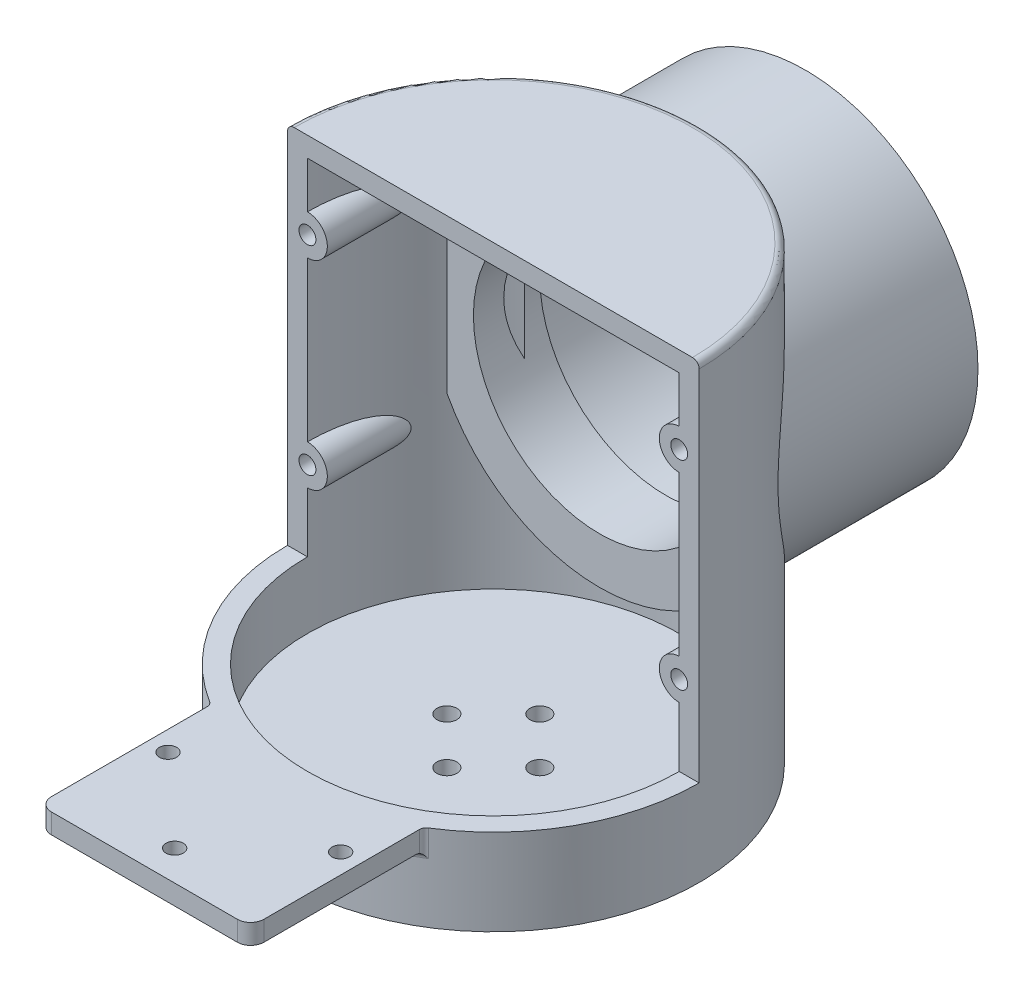
SolidWorks part; units mm, degrees
ref_plane "Спереди" through (0, 0, 0) normal (0, 0, 1) x (1, 0, 0)
ref_plane "Сверху" through (0, 0, 0) normal (0, 1, 0) x (1, 0, 0)
ref_plane "Справа" through (0, 0, 0) normal (1, 0, 0) x (0, 0, -1)
sketch "Эскиз3" plane through (0, 0, 0) normal (1, 0, 0) x (0, 0, -1)
  line L0 (0, 68.2882) -> (0, 0) construction
  line L1 (0, 0) -> (31, 0)
  line L2 (31, 0) -> (31, 68)
  line L3 (31, 68) -> (0, 68)
  line L4 (0, 68) -> (0, 65)
  line L5 (0, 65) -> (28, 65)
  line L6 (28, 65) -> (28, 3)
  line L7 (28, 3) -> (0, 3)
  line L8 (0, 3) -> (0, 0)
  dimension "D1" = 62
  dimension "D2" = 68
  dimension "D3" = 3
  dimension "D4" = 3
  dimension "D5" = 3
revolve "Повернуть2" add sketch "Эскиз3" angle 360 about L0
sketch "Эскиз4" plane through (0, 68, 0) normal (0, 1, 0) x (1, 0, 0)
  line L0 (-31, 0) -> (31, 0)
  circle A0 centre (0, 0) radius 31 construction
  arc A1 (31, 0) -> (-31, 0) centre (0, 0) cw
extrude "Вырез-Вытянуть1" cut sketch "Эскиз4" against normal blind 55
sketch "Эскиз6" plane through (0, 0, 0) normal (0, -1, 0) x (1, 0, 0)
  circle A0 centre (7, 0) radius 1.5
  dimension "D1" = 3
  dimension "D2" = 7
extrude "Вырез-Вытянуть3" cut sketch "Эскиз6" against normal up to surface (3 mm away) up to face at (0, 3, 28)
pattern_circular "Круговой массив1" count 4 over 360 about axis through (0, 68.2882, 0) along (0, 1, 0) of "Вырез-Вытянуть3"
sketch "Эскиз7" plane through (0, 0, 0) normal (0, 0, 1) x (1, 0, 0)
  circle A0 centre (0, 41) radius 21
  circle A1 centre (0, 41) radius 26
  dimension "D1" = 52
  dimension "D2" = 42
  dimension "D3" = 41
extrude "Бобышка-Вытянуть1" add sketch "Эскиз7" against normal blind 31 from offset 16 offset against normal yes
sketch "Эскиз8" plane through (0, 0, -47) normal (0, 0, -1) x (-1, 0, 0)
  circle A0 centre (0, 41) radius 21
  dimension "D1" = 42
  dimension "D2" = 41
extrude "Вырез-Вытянуть4" cut sketch "Эскиз8" against normal blind 25
sketch "Эскиз9" plane through (0, 13, 0) normal (0, 1, 0) x (1, 0, 0)
  line L0 (-16, -26.5518) -> (-16, -52.5518)
  line L1 (-16, -52.5518) -> (16, -52.5518)
  line L2 (16, -52.5518) -> (16, -26.5518)
  line L3 (0, 0) -> (0, -52.5518) construction
  arc A0 (16, -26.5518) -> (-16, -26.5518) centre (0, 0) cw
  arc A1 (-31, 0) -> (31, 0) centre (0, 0) ccw construction
  dimension "D1" = 26
  dimension "D2" = 32
extrude "Бобышка-Вытянуть2" add sketch "Эскиз9" against normal blind 3
fillet "Скругление1" radius 2 2 edges at (16, 11.5, 52.5518) (-16, 11.5, 52.5518)
fillet "Скругление2" radius 1 4 edges at (16, 11.5, 26.5518) (0, 10, 31) (-16, 11.5, 26.5518) (0, 68, -31)
sketch "Эскиз11" plane through (0, 0, 0) normal (0, 0, 1) x (1, 0, 0)
  line L0 (-28, 65) -> (-28, 13) construction
  line L1 (28, 13) -> (28, 65) construction
  line L3 (-28, 25) -> (28, 25) construction
  line L4 (-28, 25) -> (-28, 55) construction
  line L5 (-28, 55) -> (28, 55) construction
  line L6 (28, 25) -> (28, 55) construction
  circle A0 centre (-28, 55) radius 3
  circle A1 centre (-28, 25) radius 3
  circle A2 centre (28, 25) radius 3
  circle A3 centre (28, 55) radius 3
  point P12 (0, 25)
  point P15 (28, 40)
  dimension "D1" = 6
  dimension "D2" = 6
  dimension "D3" = 6
  dimension "D4" = 6
  dimension "D5" = 30
  dimension "D6" = 40
extrude "Бобышка-Вытянуть3" add sketch "Эскиз11" against normal up to surface (12.6095 mm away) up to face at (0.3812, 44.067, -10.9146)
hole_wizard "Сверло под метчик  спиральное M2.52" positions "Эскиз15" profile "Эскиз16" hole size "M2.5x0.45" standard "Ansi Metric"
sketch "Эскиз15" plane through (0, 0, 0) normal (0, 0, 1) x (1, 0, 0)
  point P0 (-28, 55)
  point P3 (28, 55)
  point P6 (28, 25)
  point P9 (-28, 25)
sketch "Эскиз16" plane through (-28, 55, 0) normal (1, 0, 0) x (0, -1, 0)
  line L0 (0, 0) -> (0, 5.7661)
  line L1 (0, 5.7661) -> (1.275, 5)
  line L2 (1.275, 5) -> (1.275, 0)
  line L5 (1.275, 0) -> (0, 0)
  line L10 (0, 5.7661) -> (-1.275, 5) construction
  line L11 (0, -6.35) -> (0, 107.95) construction
  dimension "Диаметр отверстия" = 2.55
  dimension "Глубина отверстия" = 5
  dimension "Угол заточки сверла" = 118
sketch "Эскиз17" plane through (0, 13, 0) normal (0, 1, 0) x (1, 0, 0)
  circle A0 centre (-13, -36) radius 1.3
  circle A1 centre (0, -48) radius 1.3
  circle A2 centre (13, -36) radius 1.3
  dimension "D1" = 2.6
  dimension "D2" = 36
  dimension "D3" = 12
  dimension "D4" = 13
  dimension "D5" = 26
extrude "Вырез-Вытянуть5" cut sketch "Эскиз17" against normal up to surface (3 mm away) up to face at (0, 10, 44.4581)
hole_wizard "Отверстие обработанное метчиком M2x0.41" positions "Эскиз18" profile "Эскиз19" tap size "M2x0.4" standard "HASCO Metric"
sketch "Эскиз18" plane through (0, 0, -47) normal (0, 0, -1) x (-1, 0, 0)
  line L2 (0, 41) -> (23, 41) construction
  line L4 (0, 41) -> (16.2635, 57.2635) construction
  circle A1 centre (0, 41) radius 23 construction
  point P0 (16.2635, 57.2635)
  dimension "D1" = 46
  dimension "D2" = 45
sketch "Эскиз19" plane through (-16.2635, 57.2635, -47) normal (1, 0, 0) x (0, 1, 0)
  line L0 (0, 0) -> (0, 10.4807)
  line L1 (0, 10.4807) -> (0.8, 10)
  line L2 (0.8, 10) -> (0.8, 0.225)
  line L3 (0.8, 0.225) -> (1.025, 0)
  line L5 (1.025, 0) -> (0, 0)
  line L6 (-0.8, 0.225) -> (-1.025, 0) construction
  line L10 (0, 10.4807) -> (-0.8, 10) construction
  line L11 (0, -6.35) -> (0, 107.95) construction
  dimension "Диаметр сверла" = 1.6
  dimension "Глубина сверла" = 10
  dimension "Диаметр передней зенковки" = 2.05
  dimension "Угол передней зенковки" = 90
  dimension "Угол заточки сверла" = 118
cosmetic thread "Отверстие резьбы1" parameters "D1"=8, "D2"=2
pattern_circular "Круговой массив2" count 8 over 360 about axis through (0, 41, -47) along (0, 0, 1) of "Отверстие обработанное метчиком M2x0.41"
ref_plane "Плоскость1" through (0, 0, -26) normal (0, 0, -1) x (-1, 0, 0)
sketch "Эскиз20" plane through (0, 0, -26) normal (0, 0, -1) x (-1, 0, 0)
  circle A0 centre (0, 41) radius 19
  circle A1 centre (0, 41) radius 26
  dimension "D1" = 38
  dimension "D2" = 52
extrude "Бобышка-Вытянуть6" add sketch "Эскиз20" against normal blind 10 contours A1 A0 region at (25.2646, 41, -26)
